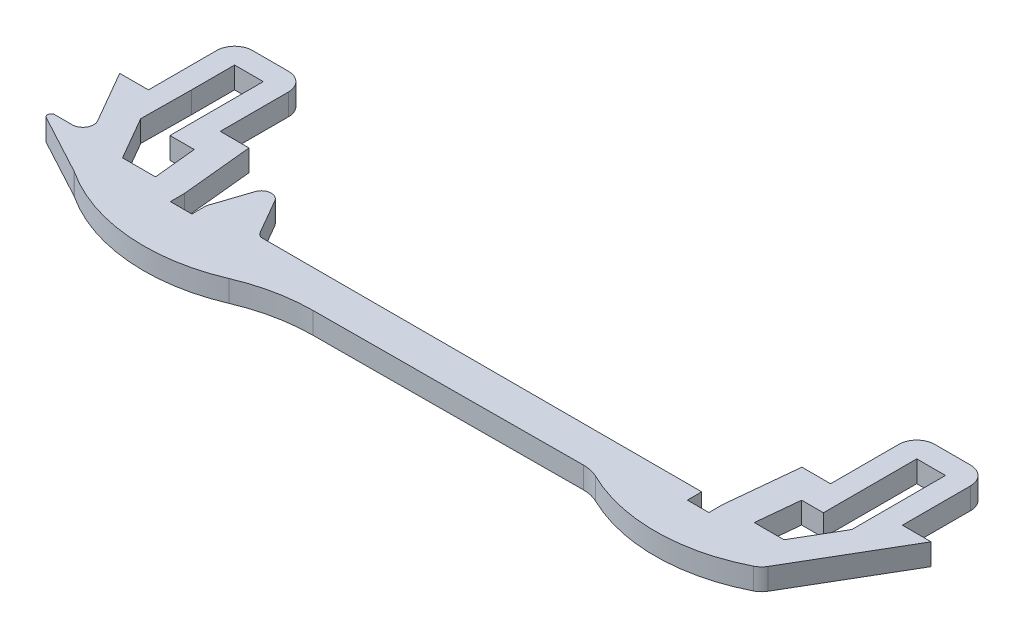
SolidWorks part; units mm, degrees
material "Custom Plastic"
ref_plane "Front Plane" through (0, 0, 0) normal (0, 0, 1) x (1, 0, 0)
ref_plane "Top Plane" through (0, 0, 0) normal (0, 1, 0) x (1, 0, 0)
ref_plane "Right Plane" through (0, 0, 0) normal (1, 0, 0) x (0, 0, -1)
sketch "Sketch1" plane through (0, 0, 0) normal (0, 1, 0) x (1, 0, 0)
  line L0 (-62.4186, -47.1902) -> (-58.4186, -47.1902)
  line L1 (-58.4186, -47.1902) -> (-58.4186, -35.1902)
  line L2 (-58.4186, -35.1902) -> (-48.4186, -35.1902)
  line L3 (-48.4186, -35.1902) -> (-48.4186, -47.1902)
  line L4 (-48.4186, -47.1902) -> (-44.4186, -47.1902)
  line L5 (-44.4186, -47.1902) -> (-43.4188, -57.1877)
  line L7 (31.5814, -57.1876) -> (32.5814, -47.1902)
  line L8 (32.5814, -47.1902) -> (36.5814, -47.1902)
  line L9 (36.5814, -47.1902) -> (36.5814, -35.1902)
  line L10 (36.5814, -35.1902) -> (46.5814, -35.1902)
  line L11 (46.5814, -35.1902) -> (46.5814, -47.1902)
  line L12 (46.5814, -47.1902) -> (50.5814, -47.1902)
  line L13 (50.5814, -47.1902) -> (41.8306, -62.1375)
  line L15 (-58.2259, -54.452) -> (-62.4186, -47.1902)
  line L16 (36.5478, -51.1902) -> (39.5814, -51.1902)
  line L17 (-55.4186, -38.1902) -> (-51.4186, -38.1902)
  line L18 (-55.4186, -38.1902) -> (-55.4186, -44.1905)
  line L20 (-51.4186, -38.1902) -> (-51.4186, -44.1902)
  line L21 (39.5814, -38.1902) -> (43.5814, -38.1902)
  line L22 (39.5814, -38.1902) -> (39.5814, -44.1902)
  line L24 (43.5814, -38.1902) -> (43.5814, -44.2297)
  line L25 (43.5814, -51.2297) -> (40.0934, -57.1876)
  line L26 (40.0934, -57.1876) -> (35.9479, -57.1876)
  line L27 (35.9479, -57.1876) -> (36.5478, -51.1902)
  line L28 (-51.4186, -51.1902) -> (-48.0385, -51.1902)
  line L29 (-48.0385, -51.1902) -> (-47.4385, -57.1902)
  line L30 (-47.4385, -57.1902) -> (-52.0263, -57.1902)
  line L31 (-52.0263, -57.1902) -> (-55.4904, -51.1902)
  line L32 (28.5814, -57.1375) -> (28.5814, -59.1375)
  line L33 (28.5814, -47.1375) -> (28.5814, -62.1375) construction
  line L34 (28.5814, -59.1375) -> (31.5814, -59.1375)
  line L35 (31.5814, -59.1375) -> (31.5814, -57.1876)
  line L36 (31.5814, -62.1375) -> (31.5814, -47.1375) construction
  line L38 (-43.4188, -57.1877) -> (-43.4188, -59.1375)
  line L39 (-43.4188, -59.1375) -> (-40.4188, -59.1375)
  line L40 (-40.4188, -59.1375) -> (-40.4188, -57.1375)
  line L41 (-33.1369, -57.1375) -> (28.5814, -57.1375)
  line L42 (-33.1369, -57.1375) -> (-36.236, -51.7698)
  line L43 (43.5814, -44.2297) -> (43.5814, -51.2297)
  line L44 (-38.7227, -52.0235) -> (-40.4188, -57.1375)
  line L45 (39.5814, -44.1902) -> (39.5814, -51.1902)
  line L46 (-55.4186, -44.1905) -> (-55.4904, -51.1902)
  line L47 (-51.4186, -44.1902) -> (-51.4186, -51.1902)
  line L48 (-53.7583, -62.1902) -> (-62.2024, -57.6422)
  line L49 (-61.9653, -56.702) -> (-59.525, -56.702)
  line L50 (30.0814, -59.1375) -> (30.0814, -65.1375) construction
  line L51 (18.3323, -62.1375) -> (-26.3407, -62.3603)
  line L52 (36.5814, -35.1902) -> (-48.4186, -35.1902) construction
  line L53 (32.5814, -47.1902) -> (-44.4186, -47.1902) construction
  arc A0 (-38.7227, -52.0235) -> (-36.236, -51.7698) centre (-37.4224, -52.4548) cw
  arc A1 (-59.525, -56.702) -> (-58.2259, -54.452) centre (-59.525, -55.202) ccw
  arc A2 (-62.2024, -57.6422) -> (-61.9653, -56.702) centre (-61.9653, -57.202) cw
  arc A3 (41.8306, -62.1375) -> (18.3323, -62.1375) centre (30.0814, -40.6305) cw
  arc A4 (-53.7583, -62.1902) -> (-26.3407, -62.3603) centre (-39.9188, -41.2179) ccw
  point P58 (30.0814, -59.1375)
  point P62 (-41.9188, -59.1375)
  dimension "D6" = 0.5
  dimension "D5" = 1.5
  dimension "D2" = 4
  dimension "D3" = 12
  dimension "D4" = 3
  dimension "D7" = 2
  dimension "D8" = 10
  dimension "D9" = 85
  dimension "D10" = 3
  dimension "D11" = 95.5889
  dimension "D12" = 3
  dimension "D13" = 3
  dimension "D14" = 3
  dimension "D15" = 3
  dimension "D16" = 14.9473
  dimension "D17" = 4
  dimension "D18" = 4
  dimension "D19" = 4
  dimension "D20" = 4
  dimension "D21" = 4
  dimension "D22" = 7.2618
  dimension "D23" = 2
  dimension "D24" = 3
  dimension "D25" = 2.4403
  dimension "D26" = 4.548
  dimension "D27" = 9.9975
  dimension "D28" = 0.9997
  dimension "D29" = 1
  dimension "D30" = 11.9473
  dimension "D31" = 4.6827
  dimension "D32" = 120
  dimension "D33" = 2.9964
  dimension "D34" = 5.114
  dimension "D35" = 4
  dimension "D36" = 4.5877
  dimension "D37" = 7
  dimension "D38" = 7
  dimension "D39" = 2
  dimension "D40" = 6
extrude "Boss-Extrude1" add sketch "Sketch1" along normal blind 3
fillet "Fillet2" radius 2.5 4 edges at (46.5814, 1.5, 35.1902) (36.5814, 1.5, 35.1902) (-58.4186, 1.5, 35.1902) (-48.4186, 1.5, 35.1902)
fillet "Fillet3" radius 1 1 edges at (-33.1369, 1.5, 57.1375)
fillet "Fillet5" radius 2.5 2 edges at (-53.7583, 1.5, 62.1902) (41.8306, 1.5, 62.1375)
fillet "Fillet6" radius 5 1 edges at (18.3323, 1.5, 62.1375)
fillet "Fillet7" radius 25 1 edges at (-26.3407, 1.5, 62.3603)
